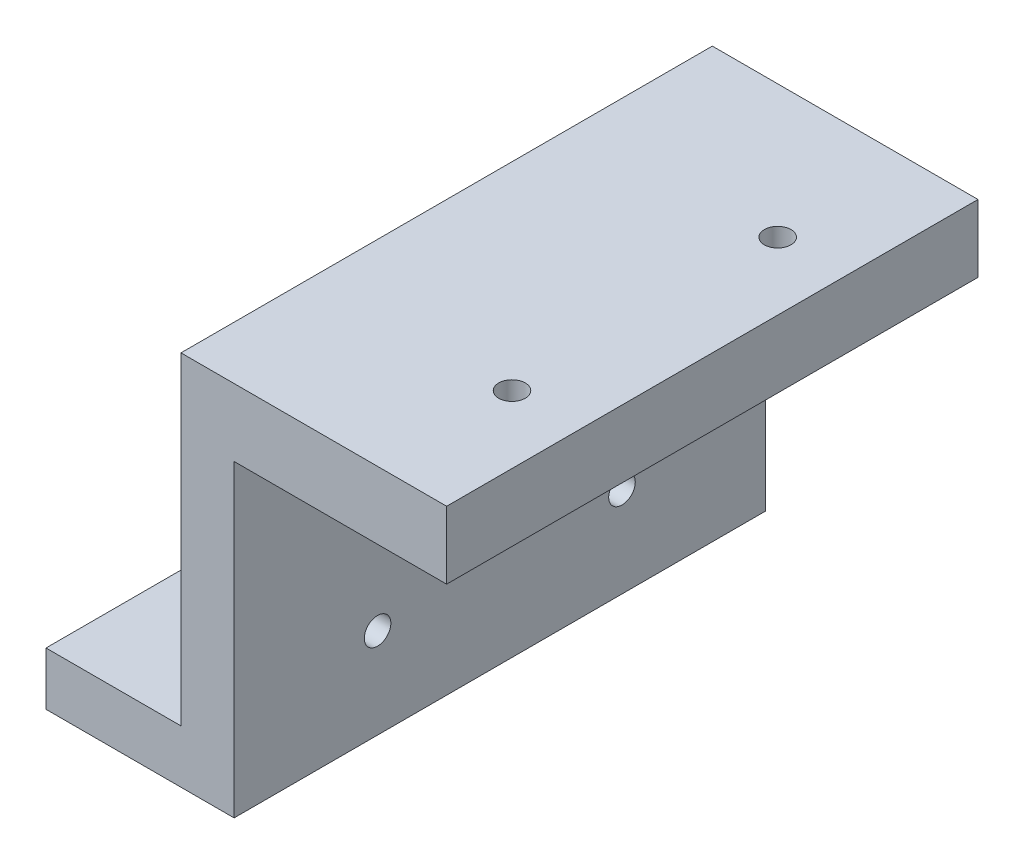
SolidWorks part; units mm, degrees
material "ABS"
ref_plane "Front Plane" through (0, 0, 0) normal (0, 0, 1) x (1, 0, 0)
ref_plane "Top Plane" through (0, 0, 0) normal (0, 1, 0) x (1, 0, 0)
ref_plane "Right Plane" through (0, 0, 0) normal (1, 0, 0) x (0, 0, -1)
sketch "Sketch1" plane through (0, 0, 0) normal (0, 0, 1) x (1, 0, 0)
  line L1 (-25, -6.35) -> (25, -6.35)
  line L2 (-25, -6.35) -> (-25, 6.35)
  line L3 (-25, 6.35) -> (25, 6.35)
  line L4 (25, -6.35) -> (25, 6.35)
  line L5 (-25, -6.35) -> (25, 6.35) construction
  line L6 (-25, 6.35) -> (25, -6.35) construction
  point P0 (0, 0)
  dimension "D1" = 12.7
  dimension "D2" = 50
extrude "Boss-Extrude1" add sketch "Sketch1" along normal blind 100
sketch "Sketch2" plane through (0, -6.35, 0) normal (0, -1, 0) x (1, 0, 0)
  line L0 (-25, 0) -> (25, 0) construction
  line L1 (-25, 100) -> (-15, 100)
  line L2 (-25, 100) -> (-25, 0)
  line L3 (-25, 0) -> (-15, 0)
  line L4 (-15, 100) -> (-15, 0)
  dimension "D1" = 10
extrude "Boss-Extrude2" add sketch "Sketch2" along normal blind 58.1
sketch "Sketch3" plane through (-25, 0, 0) normal (-1, 0, 0) x (0, 0, 1)
  line L0 (100, 6.35) -> (100, -64.45) construction
  line L1 (0, -64.45) -> (100, -64.45)
  line L2 (0, -64.45) -> (0, -54.45)
  line L3 (0, -54.45) -> (100, -54.45)
  line L4 (100, -64.45) -> (100, -54.45)
  dimension "D1" = 10
extrude "Boss-Extrude3" add sketch "Sketch3" along normal blind 25.4
sketch "Sketch4" plane through (0, 6.35, 0) normal (0, 1, 0) x (1, 0, 0)
  line L0 (25, -100) -> (-25, -100) construction
  line L1 (25, 0) -> (-0.4, 0)
  line L2 (25, 0) -> (25, -100)
  line L3 (25, -100) -> (-0.4, -100)
  line L4 (-0.4, 0) -> (-0.4, -100)
  line L5 (-0.4, -100) -> (25, 0) construction
  line L6 (12.3, -50) -> (12.3, 0) construction
  line L7 (12.3, -50) -> (12.3, -100) construction
  point P9 (12.3, -25)
  point P11 (12.3, -75)
  point P13 (12.3, -25)
  point P15 (12.3, -75)
  dimension "D1" = 25.4
sketch "Sketch7" plane through (-15, 0, 0) normal (1, 0, 0) x (0, 0, -1)
  line L0 (-100, -64.45) -> (-100, -6.35) construction
  line L1 (0, -6.35) -> (-100, -6.35)
  line L2 (0, -6.35) -> (0, -64.45)
  line L3 (0, -64.45) -> (-100, -64.45)
  line L4 (-100, -6.35) -> (-100, -64.45)
  line L8 (-50, -6.35) -> (-50, -64.45) construction
  line L11 (0, -64.45) -> (-100, -64.45) construction
  point P28 (-73, -47.45)
  point P31 (-27, -47.45)
  point P35 (-73, -29.45)
  point P37 (-27, -29.45)
  dimension "D3" = 35
  dimension "D2" = 46
  dimension "D1" = 18
hole_wizard "M5x0.8 Tapped Hole1" positions "Sketch4" profile "Sketch8" tap size "M5x0.8" standard "ANSI Metric" end condition through all
sketch "Sketch8" plane through (12.3, 6.35, 75) normal (1, 0, 0) x (0, 0, 1)
  line L0 (0, 0) -> (0, 70.8)
  line L1 (0, 70.8) -> (2.5, 70.8)
  line L2 (2.5, 70.8) -> (2.5, 0)
  line L5 (2.5, 0) -> (0, 0)
  line L11 (0, -6.35) -> (0, 107.95) construction
  dimension "Thread Major Dia." = 5
  dimension "Thru Tap Drill Depth" = 70.8
hole_wizard "M5x0.8 Tapped Hole2" positions "Sketch7" profile "Sketch9" tap size "M5x0.8" standard "ANSI Metric" end condition through all
sketch "Sketch9" plane through (-15, -29.45, 27) normal (0, 1, 0) x (0, 0, -1)
  line L0 (0, 0) -> (0, 35.4)
  line L1 (0, 35.4) -> (2.5, 35.4)
  line L2 (2.5, 35.4) -> (2.5, 0)
  line L5 (2.5, 0) -> (0, 0)
  line L11 (0, -6.35) -> (0, 107.95) construction
  dimension "Thread Major Dia." = 5
  dimension "Thru Tap Drill Depth" = 35.4
